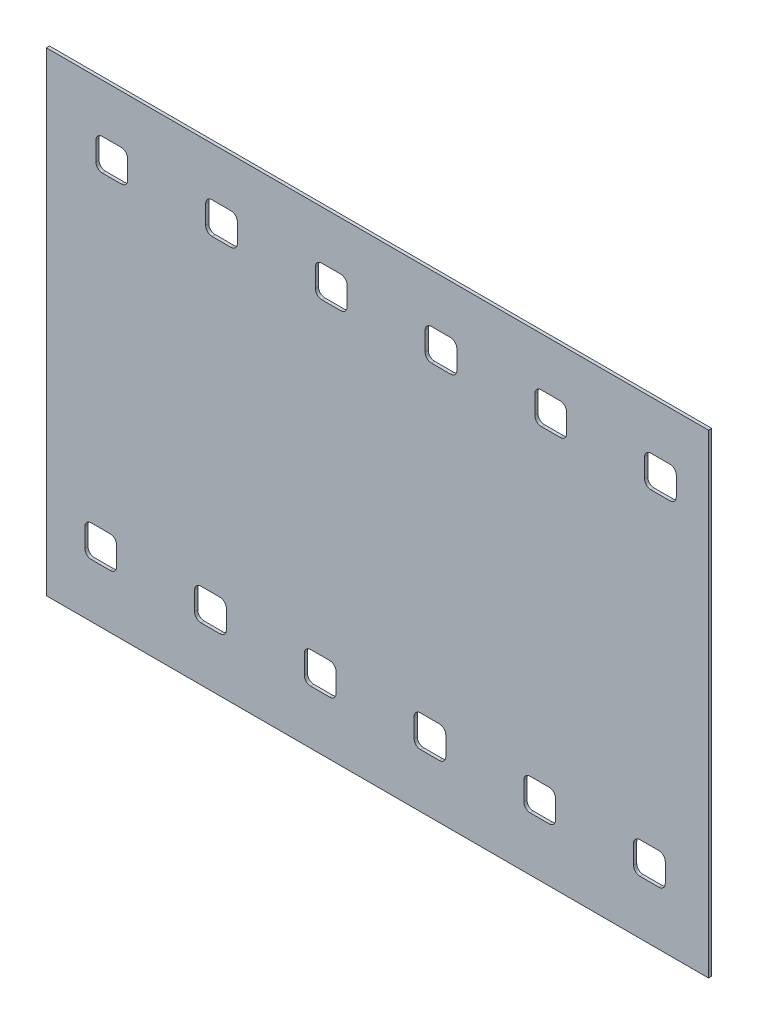
SolidWorks part; units mm, degrees
material "Custom Plastic"
ref_plane "X-Y Datum" through (0, 0, 0) normal (0, 0, 1) x (1, 0, 0)
ref_plane "X-Z Datum" through (0, 0, 0) normal (0, 1, 0) x (1, 0, 0)
ref_plane "Y-Z Datum" through (0, 0, 0) normal (1, 0, 0) x (0, 0, -1)
sketch "Sketch1" plane through (0, 0, 0) normal (0, 0, 1) x (1, 0, 0)
  line L1 (-331.7875, 237.7745) -> (331.7875, 237.7745)
  line L2 (-331.7875, 237.7745) -> (-331.7875, -237.7745)
  line L3 (-331.7875, -237.7745) -> (331.7875, -237.7745)
  line L4 (331.7875, 237.7745) -> (331.7875, -237.7745)
  line L5 (-331.7875, 237.7745) -> (331.7875, -237.7745) construction
  line L6 (-331.7875, -237.7745) -> (331.7875, 237.7745) construction
  point P0 (0, 0)
  dimension "D1" = 663.575
  dimension "D2" = 475.549
base flange "Base-Flange1" sketch "Sketch1" thickness 3.175 reverse thickness direction no parameters "D1"=1
sketch "Sketch6" plane through (0, 0, 0) normal (0, 0, 1) x (1, 0, 0)
  line L0 (272.6055, 237.7745) -> (272.6055, -237.7745) construction
  line L1 (331.7875, 237.7745) -> (-331.7875, 237.7745) construction
  line L2 (-331.7875, -237.7745) -> (331.7875, -237.7745) construction
  line L3 (331.7875, -237.7745) -> (331.7875, 237.7745) construction
  line L4 (55.1739, 0) -> (-55.1739, 0) construction
  line L5 (263.0805, -152.0495) -> (282.1305, -152.0495)
  line L6 (256.7305, -158.3995) -> (256.7305, -177.4495)
  line L7 (263.0805, -183.7995) -> (282.1305, -183.7995)
  line L8 (288.4805, -158.3995) -> (288.4805, -177.4495)
  line L9 (256.7305, -152.0495) -> (288.4805, -183.7995) construction
  line L10 (256.7305, -183.7995) -> (288.4805, -152.0495) construction
  line L11 (288.4805, 158.3995) -> (288.4805, 177.4495) construction
  line L12 (263.0805, 183.7995) -> (282.1305, 183.7995) construction
  line L13 (256.7305, 158.3995) -> (256.7305, 177.4495) construction
  line L14 (263.0805, 152.0495) -> (282.1305, 152.0495) construction
  line L15 (153.0985, 183.7995) -> (172.1485, 183.7995) construction
  line L16 (146.7485, 158.3995) -> (146.7485, 177.4495) construction
  line L17 (178.4985, 158.3995) -> (178.4985, 177.4495) construction
  line L18 (153.0985, 152.0495) -> (172.1485, 152.0495) construction
  line L19 (153.0985, -152.0495) -> (172.1485, -152.0495)
  line L20 (146.7485, -158.3995) -> (146.7485, -177.4495)
  line L21 (178.4985, -158.3995) -> (178.4985, -177.4495)
  line L22 (153.0985, -183.7995) -> (172.1485, -183.7995)
  line L23 (43.1165, 183.7995) -> (62.1665, 183.7995) construction
  line L24 (36.7665, 158.3995) -> (36.7665, 177.4495) construction
  line L25 (68.5165, 158.3995) -> (68.5165, 177.4495) construction
  line L26 (43.1165, 152.0495) -> (62.1665, 152.0495) construction
  line L27 (43.1165, -152.0495) -> (62.1665, -152.0495)
  line L28 (36.7665, -158.3995) -> (36.7665, -177.4495)
  line L29 (68.5165, -158.3995) -> (68.5165, -177.4495)
  line L30 (43.1165, -183.7995) -> (62.1665, -183.7995)
  line L31 (-66.8655, 183.7995) -> (-47.8155, 183.7995) construction
  line L32 (-73.2155, 158.3995) -> (-73.2155, 177.4495) construction
  line L33 (-41.4655, 158.3995) -> (-41.4655, 177.4495) construction
  line L34 (-66.8655, 152.0495) -> (-47.8155, 152.0495) construction
  line L35 (-66.8655, -152.0495) -> (-47.8155, -152.0495)
  line L36 (-73.2155, -158.3995) -> (-73.2155, -177.4495)
  line L37 (-41.4655, -158.3995) -> (-41.4655, -177.4495)
  line L38 (-66.8655, -183.7995) -> (-47.8155, -183.7995)
  line L39 (-176.8475, 183.7995) -> (-157.7975, 183.7995) construction
  line L40 (-183.1975, 158.3995) -> (-183.1975, 177.4495) construction
  line L41 (-151.4475, 158.3995) -> (-151.4475, 177.4495) construction
  line L42 (-176.8475, 152.0495) -> (-157.7975, 152.0495) construction
  line L43 (-176.8475, -152.0495) -> (-157.7975, -152.0495)
  line L44 (-183.1975, -158.3995) -> (-183.1975, -177.4495)
  line L45 (-151.4475, -158.3995) -> (-151.4475, -177.4495)
  line L46 (-176.8475, -183.7995) -> (-157.7975, -183.7995)
  line L47 (-286.8295, 183.7995) -> (-267.7795, 183.7995) construction
  line L48 (-293.1795, 158.3995) -> (-293.1795, 177.4495) construction
  line L49 (-261.4295, 158.3995) -> (-261.4295, 177.4495) construction
  line L50 (-286.8295, 152.0495) -> (-267.7795, 152.0495) construction
  line L51 (-286.8295, -152.0495) -> (-267.7795, -152.0495)
  line L52 (-293.1795, -158.3995) -> (-293.1795, -177.4495)
  line L53 (-261.4295, -158.3995) -> (-261.4295, -177.4495)
  line L54 (-286.8295, -183.7995) -> (-267.7795, -183.7995)
  line L55 (-331.7875, 237.7745) -> (-331.7875, -237.7745) construction
  line L56 (-275.7805, 188.8795) -> (-256.7305, 188.8795)
  line L57 (-282.1305, 182.5295) -> (-282.1305, 163.4795)
  line L58 (-275.7805, 157.1295) -> (-256.7305, 157.1295)
  line L59 (-250.3805, 182.5295) -> (-250.3805, 163.4795)
  line L60 (-282.1305, 188.8795) -> (-250.3805, 157.1295) construction
  line L61 (-282.1305, 157.1295) -> (-250.3805, 188.8795) construction
  line L62 (-165.7985, 188.8795) -> (-146.7485, 188.8795)
  line L63 (-140.3985, 182.5295) -> (-140.3985, 163.4795)
  line L64 (-165.7985, 157.1295) -> (-146.7485, 157.1295)
  line L65 (-172.1485, 182.5295) -> (-172.1485, 163.4795)
  line L66 (-55.8165, 188.8795) -> (-36.7665, 188.8795)
  line L67 (-30.4165, 182.5295) -> (-30.4165, 163.4795)
  line L68 (-55.8165, 157.1295) -> (-36.7665, 157.1295)
  line L69 (-62.1665, 182.5295) -> (-62.1665, 163.4795)
  line L70 (54.1655, 188.8795) -> (73.2155, 188.8795)
  line L71 (79.5655, 182.5295) -> (79.5655, 163.4795)
  line L72 (54.1655, 157.1295) -> (73.2155, 157.1295)
  line L73 (47.8155, 182.5295) -> (47.8155, 163.4795)
  line L74 (164.1475, 188.8795) -> (183.1975, 188.8795)
  line L75 (189.5475, 182.5295) -> (189.5475, 163.4795)
  line L76 (164.1475, 157.1295) -> (183.1975, 157.1295)
  line L77 (157.7975, 182.5295) -> (157.7975, 163.4795)
  line L78 (274.1295, 188.8795) -> (293.1795, 188.8795)
  line L79 (299.5295, 182.5295) -> (299.5295, 163.4795)
  line L80 (274.1295, 157.1295) -> (293.1795, 157.1295)
  line L81 (267.7795, 182.5295) -> (267.7795, 163.4795)
  arc A0 (256.7305, -177.4495) -> (263.0805, -183.7995) centre (263.0805, -177.4495) ccw
  arc A1 (282.1305, -183.7995) -> (288.4805, -177.4495) centre (282.1305, -177.4495) ccw
  arc A2 (282.1305, -152.0495) -> (288.4805, -158.3995) centre (282.1305, -158.3995) cw
  arc A3 (263.0805, -152.0495) -> (256.7305, -158.3995) centre (263.0805, -158.3995) ccw
  arc A4 (282.1305, 152.0495) -> (288.4805, 158.3995) centre (282.1305, 158.3995) ccw construction
  arc A5 (282.1305, 183.7995) -> (288.4805, 177.4495) centre (282.1305, 177.4495) cw construction
  arc A6 (256.7305, 177.4495) -> (263.0805, 183.7995) centre (263.0805, 177.4495) cw construction
  arc A7 (263.0805, 152.0495) -> (256.7305, 158.3995) centre (263.0805, 158.3995) cw construction
  arc A8 (146.7485, 177.4495) -> (153.0985, 183.7995) centre (153.0985, 177.4495) cw construction
  arc A9 (172.1485, 183.7995) -> (178.4985, 177.4495) centre (172.1485, 177.4495) cw construction
  arc A10 (172.1485, 152.0495) -> (178.4985, 158.3995) centre (172.1485, 158.3995) ccw construction
  arc A11 (153.0985, 152.0495) -> (146.7485, 158.3995) centre (153.0985, 158.3995) cw construction
  arc A12 (153.0985, -152.0495) -> (146.7485, -158.3995) centre (153.0985, -158.3995) ccw
  arc A13 (172.1485, -152.0495) -> (178.4985, -158.3995) centre (172.1485, -158.3995) cw
  arc A14 (172.1485, -183.7995) -> (178.4985, -177.4495) centre (172.1485, -177.4495) ccw
  arc A15 (146.7485, -177.4495) -> (153.0985, -183.7995) centre (153.0985, -177.4495) ccw
  arc A16 (36.7665, 177.4495) -> (43.1165, 183.7995) centre (43.1165, 177.4495) cw construction
  arc A17 (62.1665, 183.7995) -> (68.5165, 177.4495) centre (62.1665, 177.4495) cw construction
  arc A18 (62.1665, 152.0495) -> (68.5165, 158.3995) centre (62.1665, 158.3995) ccw construction
  arc A19 (43.1165, 152.0495) -> (36.7665, 158.3995) centre (43.1165, 158.3995) cw construction
  arc A20 (43.1165, -152.0495) -> (36.7665, -158.3995) centre (43.1165, -158.3995) ccw
  arc A21 (62.1665, -152.0495) -> (68.5165, -158.3995) centre (62.1665, -158.3995) cw
  arc A22 (62.1665, -183.7995) -> (68.5165, -177.4495) centre (62.1665, -177.4495) ccw
  arc A23 (36.7665, -177.4495) -> (43.1165, -183.7995) centre (43.1165, -177.4495) ccw
  arc A24 (-73.2155, 177.4495) -> (-66.8655, 183.7995) centre (-66.8655, 177.4495) cw construction
  arc A25 (-47.8155, 183.7995) -> (-41.4655, 177.4495) centre (-47.8155, 177.4495) cw construction
  arc A26 (-47.8155, 152.0495) -> (-41.4655, 158.3995) centre (-47.8155, 158.3995) ccw construction
  arc A27 (-66.8655, 152.0495) -> (-73.2155, 158.3995) centre (-66.8655, 158.3995) cw construction
  arc A28 (-66.8655, -152.0495) -> (-73.2155, -158.3995) centre (-66.8655, -158.3995) ccw
  arc A29 (-47.8155, -152.0495) -> (-41.4655, -158.3995) centre (-47.8155, -158.3995) cw
  arc A30 (-47.8155, -183.7995) -> (-41.4655, -177.4495) centre (-47.8155, -177.4495) ccw
  arc A31 (-73.2155, -177.4495) -> (-66.8655, -183.7995) centre (-66.8655, -177.4495) ccw
  arc A32 (-183.1975, 177.4495) -> (-176.8475, 183.7995) centre (-176.8475, 177.4495) cw construction
  arc A33 (-157.7975, 183.7995) -> (-151.4475, 177.4495) centre (-157.7975, 177.4495) cw construction
  arc A34 (-157.7975, 152.0495) -> (-151.4475, 158.3995) centre (-157.7975, 158.3995) ccw construction
  arc A35 (-176.8475, 152.0495) -> (-183.1975, 158.3995) centre (-176.8475, 158.3995) cw construction
  arc A36 (-176.8475, -152.0495) -> (-183.1975, -158.3995) centre (-176.8475, -158.3995) ccw
  arc A37 (-157.7975, -152.0495) -> (-151.4475, -158.3995) centre (-157.7975, -158.3995) cw
  arc A38 (-157.7975, -183.7995) -> (-151.4475, -177.4495) centre (-157.7975, -177.4495) ccw
  arc A39 (-183.1975, -177.4495) -> (-176.8475, -183.7995) centre (-176.8475, -177.4495) ccw
  arc A40 (-293.1795, 177.4495) -> (-286.8295, 183.7995) centre (-286.8295, 177.4495) cw construction
  arc A41 (-267.7795, 183.7995) -> (-261.4295, 177.4495) centre (-267.7795, 177.4495) cw construction
  arc A42 (-267.7795, 152.0495) -> (-261.4295, 158.3995) centre (-267.7795, 158.3995) ccw construction
  arc A43 (-286.8295, 152.0495) -> (-293.1795, 158.3995) centre (-286.8295, 158.3995) cw construction
  arc A44 (-286.8295, -152.0495) -> (-293.1795, -158.3995) centre (-286.8295, -158.3995) ccw
  arc A45 (-267.7795, -152.0495) -> (-261.4295, -158.3995) centre (-267.7795, -158.3995) cw
  arc A46 (-267.7795, -183.7995) -> (-261.4295, -177.4495) centre (-267.7795, -177.4495) ccw
  arc A47 (-293.1795, -177.4495) -> (-286.8295, -183.7995) centre (-286.8295, -177.4495) ccw
  arc A48 (-256.7305, 188.8795) -> (-250.3805, 182.5295) centre (-256.7305, 182.5295) cw
  arc A49 (-256.7305, 157.1295) -> (-250.3805, 163.4795) centre (-256.7305, 163.4795) ccw
  arc A50 (-282.1305, 163.4795) -> (-275.7805, 157.1295) centre (-275.7805, 163.4795) ccw
  arc A51 (-275.7805, 188.8795) -> (-282.1305, 182.5295) centre (-275.7805, 182.5295) ccw
  arc A52 (-146.7485, 188.8795) -> (-140.3985, 182.5295) centre (-146.7485, 182.5295) cw
  arc A53 (-146.7485, 157.1295) -> (-140.3985, 163.4795) centre (-146.7485, 163.4795) ccw
  arc A54 (-172.1485, 163.4795) -> (-165.7985, 157.1295) centre (-165.7985, 163.4795) ccw
  arc A55 (-165.7985, 188.8795) -> (-172.1485, 182.5295) centre (-165.7985, 182.5295) ccw
  arc A56 (-36.7665, 188.8795) -> (-30.4165, 182.5295) centre (-36.7665, 182.5295) cw
  arc A57 (-36.7665, 157.1295) -> (-30.4165, 163.4795) centre (-36.7665, 163.4795) ccw
  arc A58 (-62.1665, 163.4795) -> (-55.8165, 157.1295) centre (-55.8165, 163.4795) ccw
  arc A59 (-55.8165, 188.8795) -> (-62.1665, 182.5295) centre (-55.8165, 182.5295) ccw
  arc A60 (73.2155, 188.8795) -> (79.5655, 182.5295) centre (73.2155, 182.5295) cw
  arc A61 (73.2155, 157.1295) -> (79.5655, 163.4795) centre (73.2155, 163.4795) ccw
  arc A62 (47.8155, 163.4795) -> (54.1655, 157.1295) centre (54.1655, 163.4795) ccw
  arc A63 (54.1655, 188.8795) -> (47.8155, 182.5295) centre (54.1655, 182.5295) ccw
  arc A64 (183.1975, 188.8795) -> (189.5475, 182.5295) centre (183.1975, 182.5295) cw
  arc A65 (183.1975, 157.1295) -> (189.5475, 163.4795) centre (183.1975, 163.4795) ccw
  arc A66 (157.7975, 163.4795) -> (164.1475, 157.1295) centre (164.1475, 163.4795) ccw
  arc A67 (164.1475, 188.8795) -> (157.7975, 182.5295) centre (164.1475, 182.5295) ccw
  arc A68 (293.1795, 188.8795) -> (299.5295, 182.5295) centre (293.1795, 182.5295) cw
  arc A69 (293.1795, 157.1295) -> (299.5295, 163.4795) centre (293.1795, 163.4795) ccw
  arc A70 (267.7795, 163.4795) -> (274.1295, 157.1295) centre (274.1295, 163.4795) ccw
  arc A71 (274.1295, 188.8795) -> (267.7795, 182.5295) centre (274.1295, 182.5295) ccw
  point P8 (272.6055, -167.9245)
  point P39 (-266.2555, 173.0045)
  dimension "D5" = 6.35
  dimension "D9" = 6.35
  dimension "D1" = 59.182
  dimension "D2" = 69.85
  dimension "D3" = 31.75
  dimension "D4" = 31.75
  dimension "D7" = 31.75
  dimension "D8" = 31.75
  dimension "D10" = 65.532
  dimension "D11" = 64.77
  dimension "D6" = 6
  dimension "D12" = 6
extrude "Cut-Extrude1" cut sketch "Sketch6" against normal through all both and the other way through all normal cut yes
sketch "Bend-Lines1" [suppressed] plane through (0, 0, 0) normal (0, 1, 0) x (1, 0, 0)
sketch "Bounding-Box1" [suppressed] plane through (0, 0, 0) normal (0, 1, 0) x (1, 0, 0)
sheet metal parameters "Sheet-Metal1" thickness 3.175 parameters "D1"=1
flat pattern "Flat-Pattern1" [suppressed]
sketch "Bend-Lines2" plane through (0, 0, 0) normal (0, 1, 0) x (1, 0, 0)
sketch3d "Bounding-Box2" [suppressed]
  line L0 (315.9201, -237.7745, 0) -> (-315.9201, -237.7745, 0) construction
  line L1 (315.9201, 237.7745, 0) -> (-315.9201, 237.7745, 0) construction
  line L2 (315.9201, -237.7745, 0) -> (315.9201, 237.7745, 0) construction
  line L3 (-315.9201, -237.7745, 0) -> (-315.9201, 237.7745, 0) construction
sheet metal parameters "Sheet-Metal2" thickness 3.175 parameters "D1"=1
flat pattern "Flat-Pattern1"
sketch "Bend-Lines2" plane through (0, 0, 0) normal (0, 1, 0) x (1, 0, 0)
sketch3d "Bounding-Box2" [suppressed]
  line L0 (-331.7875, -237.7745, 0) -> (331.7875, -237.7745, 0) construction
  line L1 (-331.7875, 237.7745, 0) -> (331.7875, 237.7745, 0) construction
  line L2 (-331.7875, -237.7745, 0) -> (-331.7875, 237.7745, 0) construction
  line L3 (331.7875, -237.7745, 0) -> (331.7875, 237.7745, 0) construction
